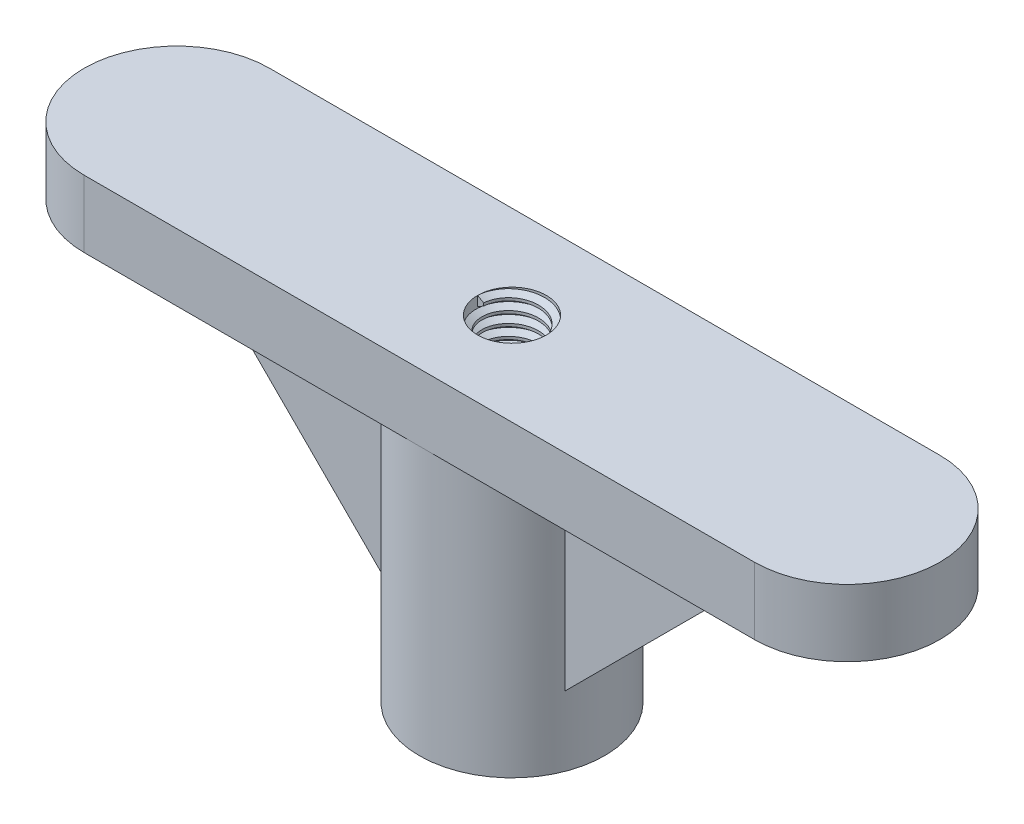
SolidWorks part; units mm, degrees
ref_plane "Front Plane" through (0, 0, 0) normal (0, 0, 1) x (1, 0, 0)
ref_plane "Top Plane" through (0, 0, 0) normal (0, 1, 0) x (1, 0, 0)
ref_plane "Right Plane" through (0, 0, 0) normal (1, 0, 0) x (0, 0, -1)
sketch "Sketch1" plane through (0, 0, 0) normal (0, 1, 0) x (1, 0, 0)
  circle A0 centre (0, 0) radius 17.5542
  circle A1 centre (0, 0) radius 6.5128
extrude "Boss-Extrude1" add sketch "Sketch1" along normal blind 50.8
sketch "Sketch2" plane through (0, 50.8, 0) normal (0, 1, 0) x (1, 0, 0)
  line L0 (-63.5, 17.5542) -> (63.5, 17.5542)
  line L1 (-63.5, -17.5542) -> (63.5, -17.5542)
  line L2 (0, 17.5542) -> (0, -17.5542) construction
  circle A0 centre (0, 0) radius 17.5542 construction
  arc A1 (-63.5, 17.5542) -> (-63.5, -17.5542) centre (-63.5, 0) ccw
  arc A2 (63.5, 17.5542) -> (63.5, -17.5542) centre (63.5, 0) cw
  circle A3 centre (0, 0) radius 6.5128 construction
  circle A4 centre (0, 0) radius 6.5128
  point P17 (0, 0)
  dimension "D1" = 127
extrude "Boss-Extrude2" add sketch "Sketch2" along normal blind 12.7 contours L0 A2 L1 A1 | A4
sketch "Sketch3" plane through (0, 0, 0) normal (0, 0, 1) x (1, 0, 0)
  line L0 (-53.975, 50.8) -> (-15.875, 12.7)
  line L1 (-15.875, 12.7) -> (-15.875, 50.8)
  line L2 (-15.875, 50.8) -> (-53.975, 50.8)
  line L3 (0, 50.8) -> (0, 0) construction
  line L4 (6.5128, 50.8) -> (-6.5128, 50.8) construction
  line L5 (15.875, 12.7) -> (15.875, 50.8)
  line L6 (53.975, 50.8) -> (15.875, 12.7)
  line L7 (15.875, 50.8) -> (53.975, 50.8)
  line L8 (-63.5, 50.8) -> (0, 50.8) construction
  point P13 (0, 0)
  point P14 (0, 0)
  point P15 (-23.4714, 9.9457)
  point P17 (-57.15, 44.3537)
  dimension "D1" = 45
  dimension "D2" = 38.1
  dimension "D3" = 9.525
extrude "Boss-Extrude3" add sketch "Sketch3" along normal mid plane 12.7
thread "Thread1" pitch 2.1167 method extrude profile "Thread Profile1" start angle 0, offset 0, length 63.5, pitch 2.1167, diameter 13.0256
ref_plane "Plane1" through (-6.5128, 63.5, 0) normal (0, 0, 1) x (-1, 0, 0)
sketch "Thread Profile1" plane through (-6.5128, 63.5, 0) normal (0, 0, 1) x (-1, 0, 0)
  line L0 (0, 0) -> (0, 2.1167) construction
  line L11 (0, 0) -> (0, 1.8521)
  line L12 (0, 1.8521) -> (-1.1457, 1.1906)
  line L13 (-1.1457, 1.1906) -> (-1.1457, 0.6615)
  line L15 (-1.1457, 0.6615) -> (0, 0)
  line L17 (-1.1457, 0.926) -> (0, 0.926) construction
  point P2 (0, 0)
  dimension "Pitch" = 2.1167
  dimension "Profile_Angle" = 60
  dimension "Profile_Land" = 0.5292
  dimension "Profile_Height" = 1.1457
